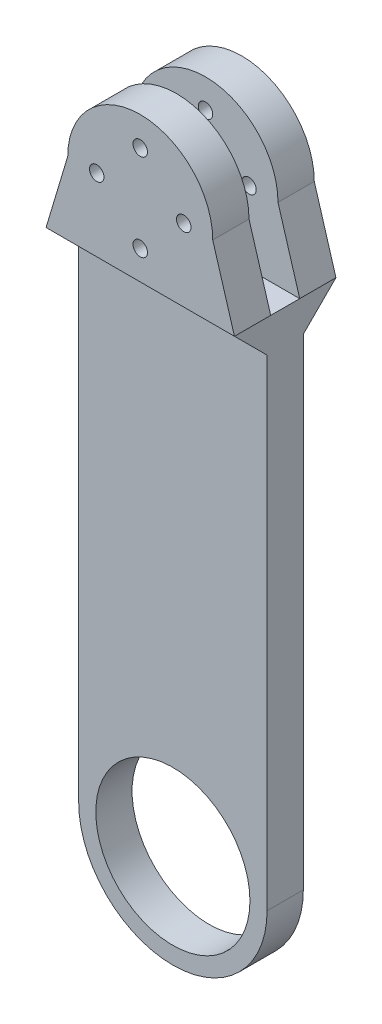
SolidWorks part; units mm, degrees
ref_plane "Front Plane" through (0, 0, 0) normal (0, 0, 1) x (1, 0, 0)
ref_plane "Top Plane" through (0, 0, 0) normal (0, 1, 0) x (1, 0, 0)
ref_plane "Right Plane" through (0, 0, 0) normal (1, 0, 0) x (0, 0, -1)
sketch "Sketch1" plane through (0, 0, 0) normal (0, 0, 1) x (1, 0, 0)
  line L0 (-16.5, 0) -> (-16.5, 90)
  line L1 (-16.5, 90) -> (16.5, 90)
  line L2 (16.5, 90) -> (16.5, 0)
  circle A0 centre (0, 0) radius 13.5
  arc A1 (-16.5, 0) -> (16.5, 0) centre (0, 0) ccw
  circle A2 centre (0, 0) radius 16.5 construction
  dimension "D1" = 27
  dimension "D3" = 90
  dimension "D2" = 3
extrude "Boss-Extrude1" add sketch "Sketch1" along normal mid plane 6.35
sketch "Sketch4" plane through (0, 0, 0) normal (0, 0, 1) x (1, 0, 0)
  line L0 (16.5, 90) -> (-16.5, 90) construction
  line L1 (-12.7, 102.7) -> (-16.5, 90)
  line L2 (12.7, 102.7) -> (16.5, 90)
  line L3 (-16.5, 90) -> (16.5, 90)
  arc A0 (12.7, 102.7) -> (-12.7, 102.7) centre (0, 102.7) ccw
  circle A1 centre (0, 110.32) radius 1.27
  circle A2 centre (7.62, 102.7) radius 1.27
  circle A3 centre (0, 95.08) radius 1.27
  circle A4 centre (-7.62, 102.7) radius 1.27
  dimension "D1" = 25.4
  dimension "D2" = 2.54
  dimension "D3" = 7.62
  dimension "D4" = 4
extrude "Boss-Extrude2" add sketch "Sketch4" along normal mid plane 17.78
chamfer "Chamfer1" distance 5.71 angle 45 2 edges at (0, 90, 3.175) (0, 90, -3.175)
sketch "Sketch5" plane through (0, 0, 0) normal (0, 0, 1) x (1, 0, 0)
  line L0 (-12.7, 102.7) -> (-16.5, 90)
  line L1 (-16.5, 90) -> (16.5, 90)
  line L2 (16.5, 90) -> (12.7, 102.7)
  arc A0 (12.7, 102.7) -> (-12.7, 102.7) centre (0, 102.7) ccw
extrude "Cut-Extrude1" cut sketch "Sketch5" against normal mid plane 5.08
